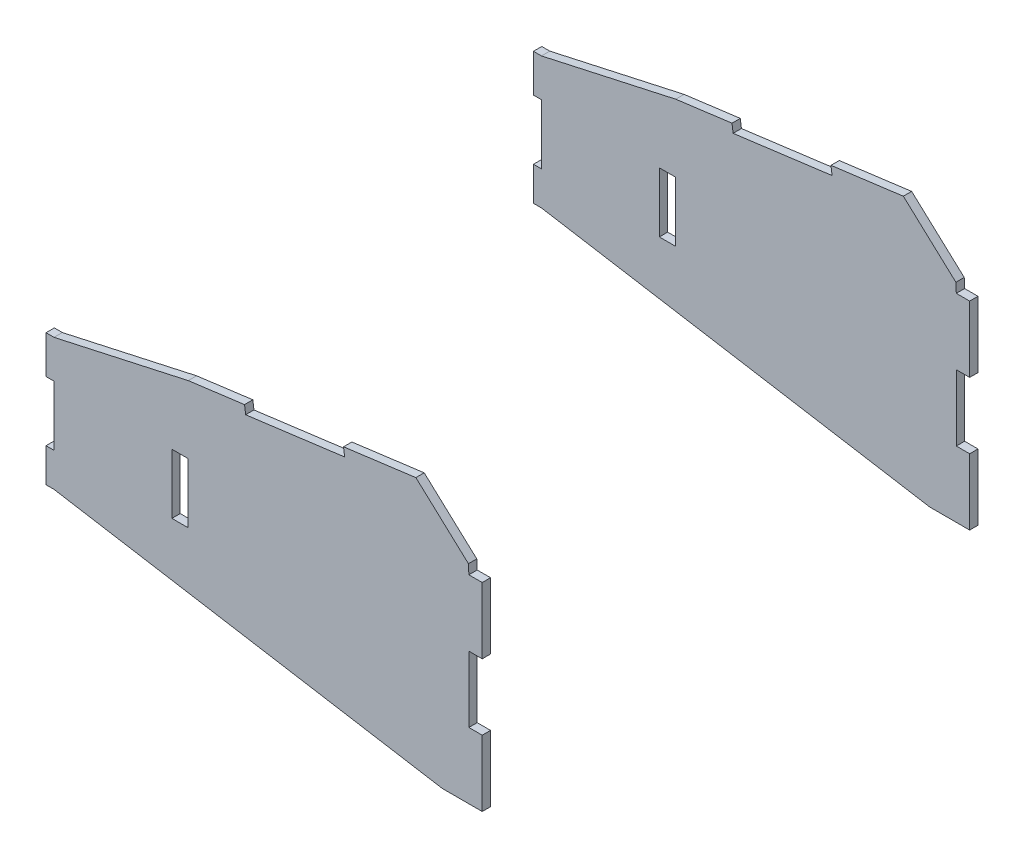
SolidWorks part; units mm, degrees
note: The reader was unsure of these and kept them because the rebuilt part matched: shared geometry of "Sketch1<6>".
ref_plane "Front Plane" through (0, 0, 0) normal (0, 0, 1) x (1, 0, 0)
ref_plane "Top Plane" through (0, 0, 0) normal (0, 1, 0) x (1, 0, 0)
ref_plane "Right Plane" through (0, 0, 0) normal (1, 0, 0) x (0, 0, -1)
sketch "Sketch1" plane through (0, 0, 0) normal (0, 0, 1) x (1, 0, 0)
  line L5 (-0.5142, -82.2846) -> (-67.4053, -20.8958)
  line L6 (17, -346.6142) -> (17, -262.5006)
  line L7 (17, -262.5006) -> (0, -262.5006)
  line L8 (0, -262.5006) -> (0, -178.3871)
  line L9 (0, -178.3871) -> (17, -178.3871)
  line L10 (17, -178.3871) -> (17, -94.2735)
  line L11 (17, -94.2735) -> (0, -94.2735)
  line L12 (0, -94.2735) -> (-0.5142, -82.2846)
  line L13 (-0.0093, -22.7659) -> (-451.7589, -81.8874) construction
  line L14 (-0.0093, -22.7659) -> (-457.8638, -82.6864) construction
  line L16 (-67.4053, -20.8958) -> (14.6273, -10.16) construction
  line L17 (-357.0192, -58.7982) -> (-357.0192, -292.6159) construction
  line L18 (-324.0897, -270.1118) -> (-9.2742, -228.9112) construction
  line L19 (-377.8472, -63.3989) -> (-377.8472, -289.1363) construction
  line L20 (17, -262.5006) -> (17, -178.3871) construction
  line L21 (2053.0716, -10.16) -> (0, -10.16) construction
  line L22 (2053.0716, -10.16) -> (0, -10.16) construction
  line L23 (-285.3906, -49.424) -> (-284.0151, -59.9344)
  line L24 (-284.0151, -59.9344) -> (-158.0889, -43.4541)
  line L25 (-158.0889, -43.4541) -> (-159.4644, -32.9438)
  line L26 (-285.3906, -49.424) -> (-357.0192, -58.7982)
  line L32 (-33.8, -346.6142) -> (-527.8472, -264.0768)
  line L33 (-527.8472, -96.5324) -> (-527.8472, -264.0768) construction
  line L34 (-538.0072, -96.5324) -> (-538.0072, -264.0768) construction
  line L39 (-357.0192, -58.7982) -> (-527.8472, -96.5324)
  line L41 (-357.0192, -58.7982) -> (-357.0192, -378.0499) construction
  line L42 (-35.6426, -27.4293) -> (-9.2742, -228.9112) construction
  line L43 (-350.458, -68.6299) -> (-324.0897, -270.1118) construction
  line L44 (-527.8472, -58.7982) -> (-527.8472, -378.0499) construction
  line L45 (-538.0072, -58.7982) -> (-538.0072, -378.0499) construction
  line L46 (-67.4053, -20.8958) -> (-159.4644, -32.9438)
  line L47 (-377.8472, -58.7982) -> (-377.8472, -378.0499) construction
  line L48 (-1.3848, -12.2555) -> (-459.2393, -72.176) construction
  line L49 (-9.1947, -382.6004) -> (-55.3393, -30.0071) construction
  line L50 (0, -346.6142) -> (10.16, -346.6142) construction
  line L51 (-33.8, -346.6142) -> (17, -346.6142)
  line L52 (-538.0072, -221.017) -> (-527.8472, -221.017)
  line L54 (-538.0072, -221.017) -> (-357.0192, -221.017) construction
  line L55 (-538.0072, -144.817) -> (-357.0192, -144.817) construction
  line L56 (-527.8472, -96.5324) -> (-538.0072, -96.5324)
  line L57 (-357.0192, -221.017) -> (-377.8472, -221.017)
  line L58 (-357.0192, -221.017) -> (-357.0192, -144.817)
  line L59 (-357.0192, -144.817) -> (-377.8472, -144.817)
  line L60 (-377.8472, -221.017) -> (-377.8472, -144.817)
  line L61 (-527.8472, -264.0768) -> (-538.0072, -264.0768)
  line L62 (-538.0072, -264.0768) -> (-538.0072, -221.017)
  line L63 (-527.8472, -221.017) -> (-527.8472, -144.817)
  line L64 (-527.8472, -144.817) -> (-538.0072, -144.817)
  line L65 (-538.0072, -144.817) -> (-538.0072, -96.5324)
  spline S0 degree 3 poles (-0.0115, -86.2) (-0.0115, -35.7052) (-0.0087, 0) (-0.0048, 0) knots 0 0 0 0 1 1 1 1 weights 1 0.804738 0.804738 1 construction
  point P27 (-158.7766, -38.199)
  point P29 (-361.1687, -410.6894)
  point P31 (-357.0192, -56.4466)
  point P33 (-381.4111, -412.463)
  point P34 (-412.4492, -58.2202)
  point P35 (-521.1558, -424.7072)
  point P36 (-552.1938, -70.4643)
  point P57 (-573, -182.917)
  line B0 (-377.8472, -257.5196) -> (-604.724, -257.5196) construction
  dimension "D2" = 10.6
  dimension "D3" = 14.6273
  dimension "D4" = 355.6
  dimension "D5" = 20.828
  dimension "D9" = 50.8
  dimension "D10" = 203.2
  dimension "D11" = 127
  dimension "D12" = 185
  dimension "D14" = 76.2
  dimension "D15" = 135
  dimension "D16" = 85
  dimension "D17" = 12
  dimension "D18" = 17
  dimension "D7" = 10.16
  dimension "D20" = 317.5
  dimension "D6" = 150
sketch_block_instance "Block1-1"
sketch_block "Block1"
extrude "Boss-Extrude6" add sketch "Sketch1" along normal blind 10.6 from vertex at 304.8
extrude "Boss-Extrude7" add sketch "Sketch1<6>" along normal blind 10.6 from vertex separate body
sketch "Sketch1<6>" plane through (0, 0, 0) normal (0, 0, 1) x (1, 0, 0) same geometry as "Sketch1"
